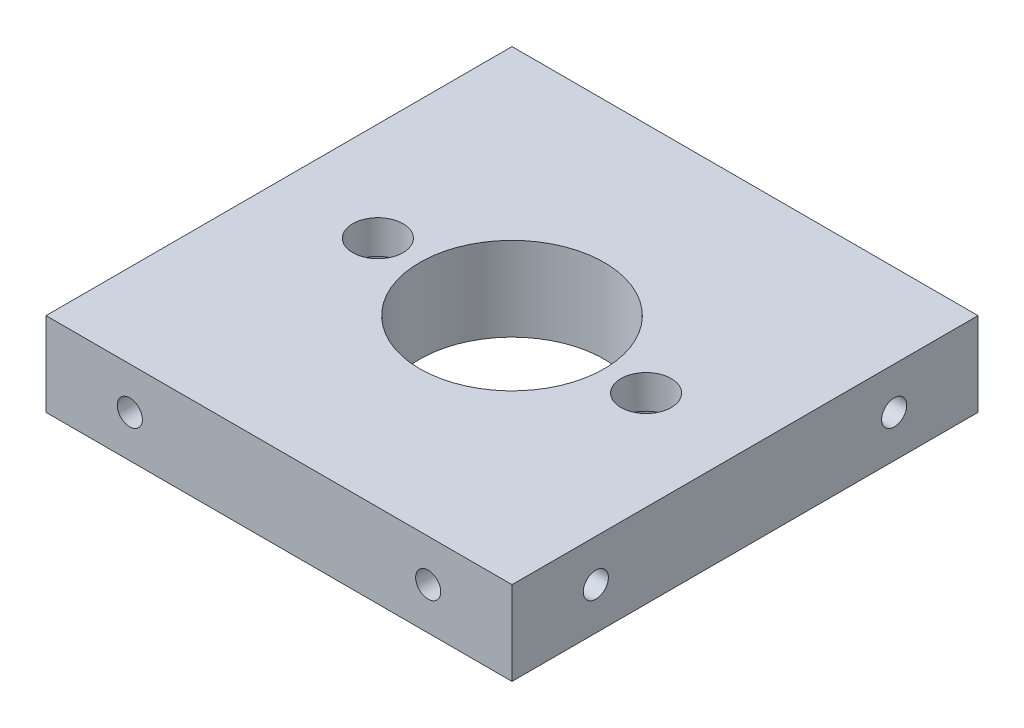
SolidWorks part; units mm, degrees
ref_plane "前视基准面" through (0, 0, 0) normal (0, 0, 1) x (1, 0, 0)
ref_plane "上视基准面" through (0, 0, 0) normal (0, 1, 0) x (1, 0, 0)
ref_plane "右视基准面" through (0, 0, 0) normal (1, 0, 0) x (0, 0, -1)
other "Configuration Table"
sketch "草图1" plane through (0, 0, 0) normal (0, 1, 0) x (1, 0, 0)
  line L0 (5.9, 0) -> (21.9, 0)
  line L1 (0, -13.9) -> (27.8, -13.9)
  line L2 (0, -13.9) -> (0, 13.9)
  line L3 (0, 13.9) -> (27.8, 13.9)
  line L4 (27.8, -13.9) -> (27.8, 13.9)
  circle A0 centre (13.9, 0) radius 5.5
  circle A2 centre (5.9, 0) radius 1.5
  circle A3 centre (21.9, 0) radius 1.5
  circle A8 centre (5.9, 0) radius 2.25
  circle A9 centre (21.9, 0) radius 2.25
  point P0 (0, 0)
  point P10 (13.9, 13.9)
  point P13 (0, 0)
  point P18 (0, 0)
  dimension "D1" = 27.8
  dimension "D2" = 27.8
  dimension "D3" = 11
  dimension "D4" = 16
  dimension "D5" = 4.5
  dimension "D6" = 3
extrude "凸台-拉伸1" add sketch "草图1" along normal blind 5 contours L1 L4 L3 L2 | A0
extrude "切除-拉伸1" cut sketch "草图1<15>" along normal through all contours A2 | A3
sketch "草图1<15>" plane through (0, 0, 0) normal (0, 1, 0) x (1, 0, 0) same geometry as "草图1"
extrude "切除-拉伸2" cut sketch "草图1<16>" along normal offset from surface (3 mm away) 2 contours A9 | A8 up to face at (5.9, 5, 1.5)
sketch "草图1<16>" plane through (0, 0, 0) normal (0, 1, 0) x (1, 0, 0) same geometry as "草图1"
sketch "草图2" plane through (0, 0, -13.9) normal (0, 0, -1) x (-1, 0, 0)
  line L0 (0, 5) -> (0, 0) construction
  line L1 (-27.8, 5) -> (-27.8, 0) construction
  circle A0 centre (-22.8, 2.5) radius 0.75
  circle A1 centre (-5, 2.5) radius 0.75
  point P4 (0, 0)
  point P7 (0, 2.5)
  dimension "D1" = 1.5
  dimension "D2" = 5
  dimension "D3" = 5
extrude "切除-拉伸3" cut sketch "草图2" against normal blind 4 contours A0 | A1
extrude "切除-拉伸4" cut sketch "草图2<3>" along normal blind 4 from surface contours A1 | A0 starting at face at (13.9, 2.5, 13.9)
sketch "草图2<3>" plane through (0, 0, -13.9) normal (0, 0, -1) x (-1, 0, 0) same geometry as "草图2"
sketch "草图3" plane through (0, 0, 0) normal (-1, 0, 0) x (0, 0, 1)
  line L0 (13.9, 5) -> (13.9, 0) construction
  line L1 (-13.9, 5) -> (-13.9, 0) construction
  circle A0 centre (-8.9, 2.5) radius 0.75
  circle A1 centre (8.9, 2.5) radius 0.75
  point P6 (13.9, 2.5)
  dimension "D1" = 1.5
  dimension "D2" = 5
  dimension "D3" = 5
extrude "切除-拉伸5" cut sketch "草图3" against normal blind 4 contours A0 | A1
extrude "切除-拉伸6" cut sketch "草图3<3>" along normal blind 4 from surface contours A0 | A1 starting at face at (27.8, 2.5, 0)
sketch "草图3<3>" plane through (0, 0, 0) normal (-1, 0, 0) x (0, 0, 1) same geometry as "草图3"
